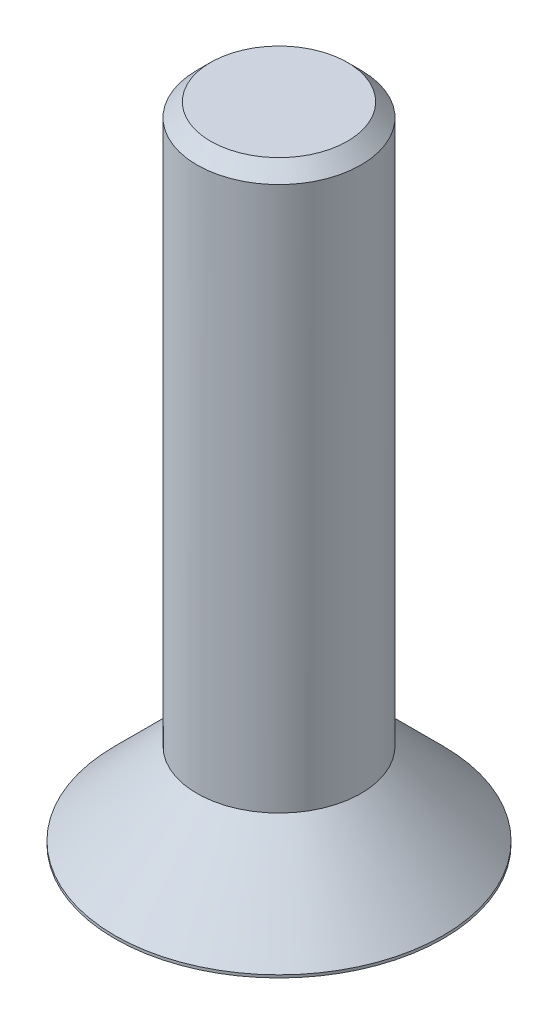
SolidWorks part; units mm, degrees
ref_plane "Front Plane" through (0, 0, 0) normal (0, 0, 1) x (1, 0, 0)
ref_plane "Top Plane" through (0, 0, 0) normal (0, 1, 0) x (1, 0, 0)
ref_plane "Right Plane" through (0, 0, 0) normal (1, 0, 0) x (0, 0, -1)
sketch "Sketch1" plane through (0, 0, 0) normal (0, 1, 0) x (1, 0, 0)
  circle A0 centre (0, 0) radius 3
  dimension "D1" = 6
extrude "Boss-Extrude1" add sketch "Sketch1" along normal blind 1.75
sketch "Sketch2" plane through (0, 1.75, 0) normal (0, 1, 0) x (1, 0, 0)
  circle A0 centre (0, 0) radius 1.5
  dimension "D1" = 3
extrude "Boss-Extrude2" add sketch "Sketch2" along normal blind 10
chamfer "Chamfer1" distance 1.7 angle 45 1 edges at (0, 1.75, 3)
chamfer "Chamfer2" distance 0.25 angle 45 1 edges at (0, 11.75, 1.5)
equation "\"1i75\"=10"
